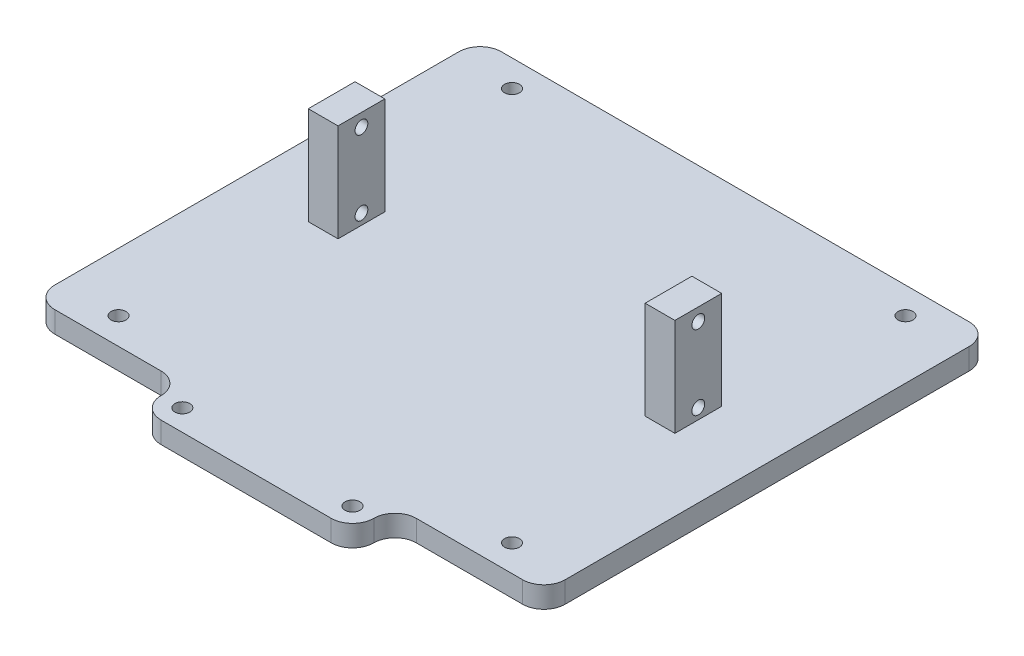
SolidWorks part; units mm, degrees
ref_plane "정면" through (0, 0, 0) normal (0, 0, 1) x (1, 0, 0)
ref_plane "윗면" through (0, 0, 0) normal (0, 1, 0) x (1, 0, 0)
ref_plane "우측면" through (0, 0, 0) normal (1, 0, 0) x (0, 0, -1)
sketch "스케치1" plane through (0, 0, 0) normal (0, 1, 0) x (1, 0, 0)
  line L0 (-25, -52.5) -> (-60, -52.5)
  line L1 (60, 52.5) -> (-60, 52.5)
  line L2 (60, 52.5) -> (60, -52.5)
  line L3 (60, -52.5) -> (25, -52.5)
  line L4 (-60, 52.5) -> (-60, -52.5)
  line L5 (60, 52.5) -> (-60, -52.5) construction
  line L6 (60, -52.5) -> (-60, 52.5) construction
  line L7 (25, -62.5) -> (-25, -62.5)
  line L8 (25, -62.5) -> (25, -52.5)
  line L10 (-25, -62.5) -> (-25, -52.5)
  line L11 (25, -62.5) -> (-25, -52.5) construction
  line L12 (25, -52.5) -> (-25, -62.5) construction
  point P0 (0, 0)
  point P6 (0, -57.5)
  dimension "D1" = 120
  dimension "D2" = 105
  dimension "D3" = 50
  dimension "D4" = 10
extrude "보스-돌출1" add sketch "스케치1" along normal blind 5
fillet "필렛1" radius 5 8 edges at (60, 2.5, -52.5) (60, 2.5, 52.5) (-60, 2.5, -52.5) (-60, 2.5, 52.5) (-25, 2.5, 52.5) (25, 2.5, 52.5) (25, 2.5, 62.5) (-25, 2.5, 62.5)
sketch "스케치2" plane through (0, 5, 0) normal (0, 1, 0) x (1, 0, 0)
  line L0 (-43.1, 29.5) -> (-43.1, -5.3) construction
  line L1 (-36.1, -4.8) -> (-43.1, -4.8)
  line L2 (-36.1, -4.8) -> (-36.1, 6.2)
  line L3 (-36.1, 6.2) -> (-43.1, 6.2)
  line L4 (-43.1, -4.8) -> (-43.1, 6.2)
  line L5 (-61.9, -0.8) -> (-43.1, -0.8) construction
  line L6 (-43.1, 2.2) -> (-61.9, 2.2) construction
  dimension "D1" = 7
  dimension "D2" = 4
  dimension "D3" = 4
extrude "보스-돌출2" add sketch "스케치2" along normal blind 23 separate body
sketch "스케치3" plane through (-36.1, 0, 0) normal (1, 0, 0) x (0, 0, -1)
  circle A0 centre (0.7, 7.5) radius 1.5 construction
  circle A1 centre (0.7, 25) radius 1.5 construction
  circle A4 centre (0.7, 7.5) radius 1.5
  circle A5 centre (0.7, 25) radius 1.5
extrude "컷-돌출1" cut sketch "스케치3" against normal through all
mirror "대칭 복사1" about plane through (0, 0, 0) normal (1, 0, 0) of bodies 103
sketch "스케치5" plane through (0, 5, 0) normal (0, 1, 0) x (1, 0, 0)
  circle A0 centre (-46.25, -46.25) radius 1.75 construction
  circle A1 centre (-46.25, 46.25) radius 1.75 construction
  circle A2 centre (46.25, 46.25) radius 1.75 construction
  circle A3 centre (46.25, -46.25) radius 1.75 construction
  circle A4 centre (-46.25, -46.25) radius 1.75
  circle A5 centre (-46.25, 46.25) radius 1.75
  circle A6 centre (46.25, 46.25) radius 1.75
  circle A7 centre (46.25, -46.25) radius 1.75
extrude "컷-돌출3" cut sketch "스케치5" against normal through all
sketch "스케치6" plane through (0, 5, 0) normal (0, 1, 0) x (1, 0, 0)
  circle A0 centre (20, -57.5) radius 1.75 construction
  circle A1 centre (-20, -57.5) radius 1.75 construction
  circle A2 centre (20, -57.5) radius 1.75
  circle A3 centre (-20, -57.5) radius 1.75
extrude "컷-돌출4" cut sketch "스케치6" against normal through all
